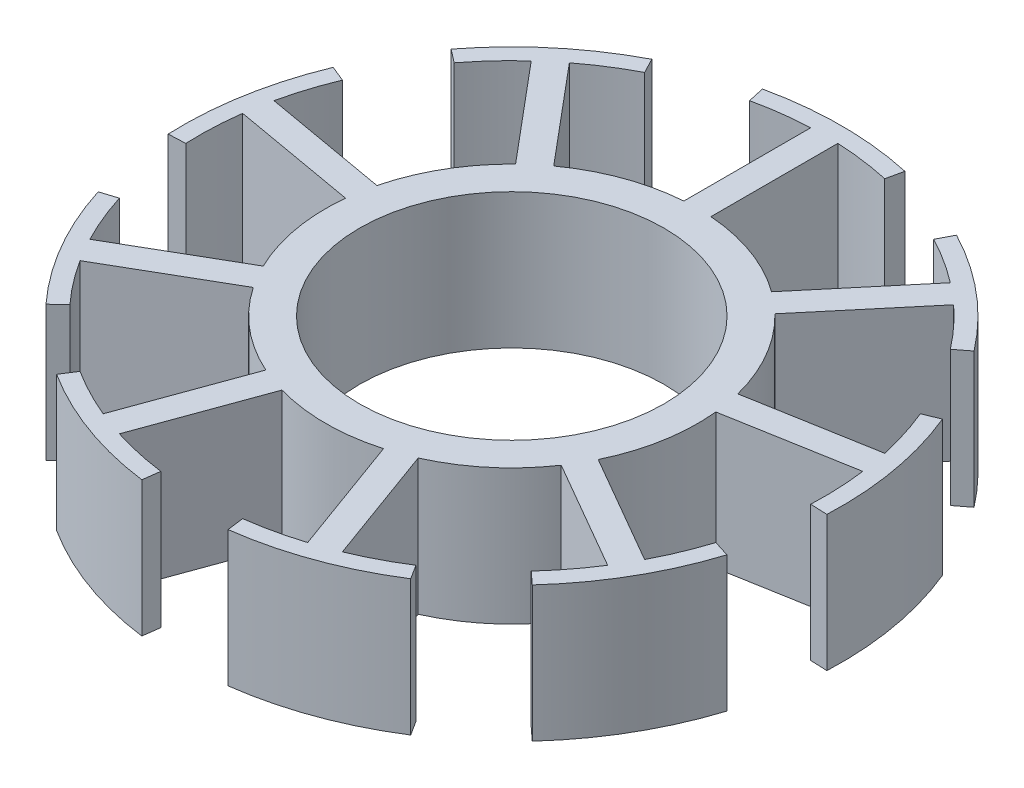
SolidWorks part; units mm, degrees
note: The reader was unsure of these and kept them because the rebuilt part matched: shared geometry of "Sketch1<3>".
ref_plane "Front Plane" through (0, 0, 0) normal (0, 0, 1) x (1, 0, 0)
ref_plane "Top Plane" through (0, 0, 0) normal (0, 1, 0) x (1, 0, 0)
ref_plane "Right Plane" through (0, 0, 0) normal (1, 0, 0) x (0, 0, -1)
sketch "Sketch1" plane through (0, 0, 0) normal (0, 1, 0) x (1, 0, 0)
  line L0 (-0.8, 10.9699) -> (-0.8, 18.4699)
  line L1 (0, 0) -> (0, 13.6776) construction
  line L2 (-3.9951, 18.0504) -> (-4.2112, 19.0268)
  line L3 (0.8, 10.9699) -> (0.8, 18.4699)
  line L4 (3.9951, 18.0504) -> (4.2112, 19.0268)
  circle A0 centre (0, 0) radius 9
  circle A1 centre (0, 0) radius 11
  arc A2 (-0.8, 18.4699) -> (-3.9951, 18.0504) centre (0, 0) ccw
  arc A3 (0.8, 18.4699) -> (3.9951, 18.0504) centre (0, 0) cw
  arc A4 (-4.2112, 19.0268) -> (4.2112, 19.0268) centre (0, 0) cw
  dimension "D1" = 18
  dimension "D2" = 2
  dimension "D3" = 7.5
  dimension "D4" = 0.8
extrude "Boss-Extrude1" add sketch "Sketch1" along normal blind 8
extrude "Boss-Extrude4" add sketch "Sketch1<3>" along normal blind 8
sketch "Sketch1<3>" plane through (0, 0, 0) normal (0, 1, 0) x (1, 0, 0) same geometry as "Sketch1"
pattern_circular "CirPattern2" count 9 over 360 about axis through (0, 0, 0) along (0, 1, 0) of "Boss-Extrude4"
